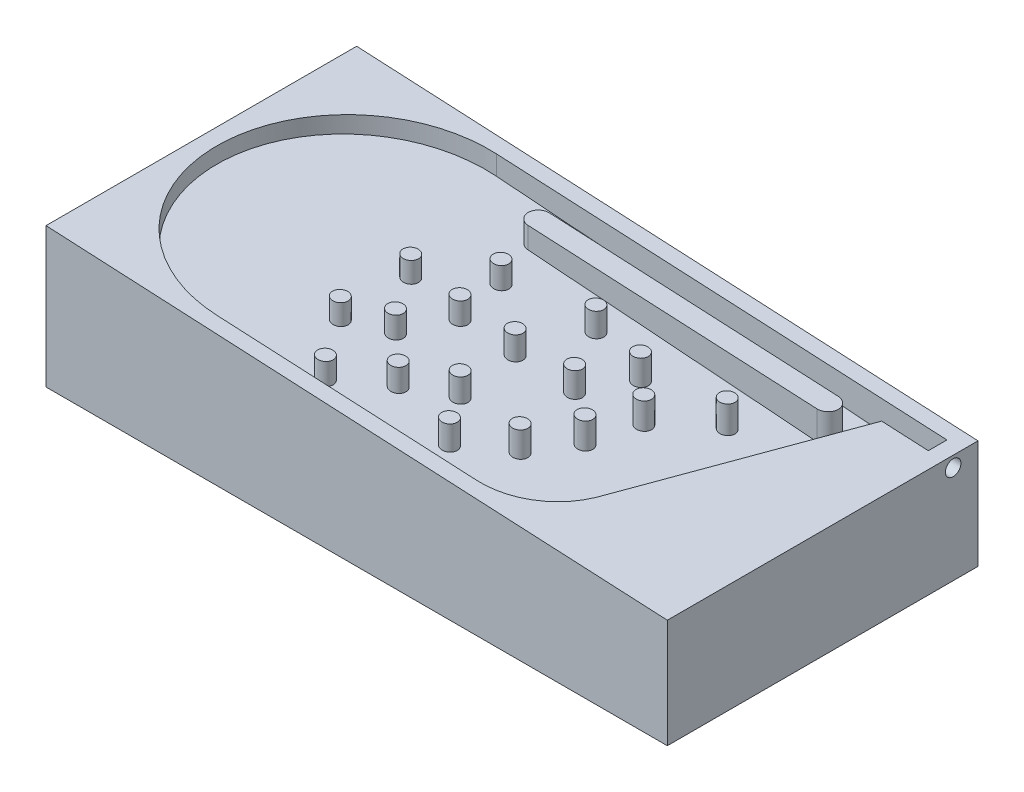
SolidWorks part; units mm, degrees
note: The reader was unsure of these and kept them because the rebuilt part matched: shared geometry of "草圖4<5>".
ref_plane "前基準面" through (0, 0, 0) normal (0, 0, 1) x (1, 0, 0)
ref_plane "上基準面" through (0, 0, 0) normal (0, 1, 0) x (1, 0, 0)
ref_plane "右基準面" through (0, 0, 0) normal (1, 0, 0) x (0, 0, -1)
sketch "草圖2" plane through (0, 0, 0) normal (0, 0, 1) x (1, 0, 0)
  line L0 (0, 0) -> (0, 20)
  line L1 (0, 20) -> (40, 15)
  line L2 (40, 15) -> (40, 0)
  line L3 (40, 0) -> (0, 0)
  dimension "D1" = 20
  dimension "D2" = 15
  dimension "D3" = 40
extrude "填料-伸長1" add sketch "草圖2" along normal blind 20
sketch "草圖4" plane through (1.2355, 0, 0) normal (0, 1, 0) x (1, 0, 0)
  line L0 (8.7645, -1) -> (37.7645, -1)
  line L1 (-1.2355, 0) -> (38.7645, 0)
  line L2 (-1.2355, 0) -> (-1.2355, -20)
  line L3 (-1.2355, -20) -> (38.7645, -20)
  line L4 (38.7645, 0) -> (38.7645, -20)
  line L5 (37.7645, -1) -> (37.7645, -19)
  line L6 (37.7645, -19) -> (8.7645, -19)
  line L7 (30.0533, -15.8981) -> (34.7645, -2.2)
  line L8 (34.7645, -2.2) -> (37.7645, -2.2)
  line L10 (13.5383, -3.0403) -> (32.1165, -3.0403) construction
  line L11 (13.5383, -2.3498) -> (32.1165, -2.3498)
  line L12 (13.5383, -3.7307) -> (32.1165, -3.7307)
  arc A0 (25.5012, -19) -> (30.0533, -15.8981) centre (25.5012, -14.1088) ccw
  arc A1 (8.7645, -1) -> (8.7645, -19) centre (8.7645, -10) ccw
  arc A2 (13.5383, -2.3498) -> (13.5383, -3.7307) centre (13.5383, -3.0403) ccw
  arc A3 (32.1165, -3.7307) -> (32.1165, -2.3498) centre (32.1165, -3.0403) ccw
  circle A4 centre (14.4844, -6.4264) radius 0.5
  circle A5 centre (13.8801, -12.6158) radius 0.5
  circle A6 centre (18.5976, -9.6298) radius 0.5
  circle A7 centre (23.6787, -6.6424) radius 0.5
  circle A8 centre (23.7982, -14.5127) radius 0.5
  circle A9 centre (19.1466, -13.7191) radius 0.5
  circle A10 centre (22.3213, -9.5254) radius 0.5
  circle A11 centre (26.0528, -8.8039) radius 0.5
  circle A12 centre (25.3141, -11.8509) radius 0.5
  circle A13 centre (28.7712, -6.1514) radius 0.5
  circle A14 centre (19.8197, -5.6517) radius 0.5
  circle A15 centre (11.4442, -9.1995) radius 0.5
  circle A16 centre (11.5291, -13.8176) radius 0.5
  circle A17 centre (14.1931, -17.4411) radius 0.5
  circle A18 centre (16.7337, -15.2955) radius 0.5
  circle A19 centre (21.3118, -16.5748) radius 0.5
  circle A20 centre (15.105, -9.6896) radius 0.5
  point P15 (22.8274, -3.0403)
  point P57 (0, 0)
  dimension "D1" = 1
  dimension "D2" = 29
  dimension "D7" = 18
  dimension "D8" = 1
  dimension "D3" = 1
  dimension "D4" = 3
  dimension "D5" = 1.2
  dimension "D6" = 1
sketch "草圖5" plane through (0, 0, 20) normal (0, 0, 1) x (1, 0, 0)
  line L0 (0, 20) -> (40, 15)
  line L1 (40, 15) -> (40, 7)
  line L2 (40, 0) -> (40, 15) construction
  line L3 (0, 20) -> (0, 7)
  line L4 (0, 20) -> (0, 0) construction
  line L5 (0, 7) -> (40, 7)
  point P2 (0, 20)
  point P4 (0, 0)
  point P11 (1.0622, 15)
  dimension "D1" = 8
extrude "除料-伸長6" cut sketch "草圖4" against normal blind 15 from offset 20 contours A1 L6 L5 L0 | A15 | A16 | A17 | A5 | A20 | A4 | A18 | A9 | A19 | A6 | A14 | A10 | A7 | A11 | A12 | A8 | A13 | L12 A3 L11 A2
extrude "填料-伸長2" add sketch "草圖4<5>" along normal blind 10 contours L6 A0 L7 L8 L5
sketch "草圖4<5>" plane through (1.2355, 0, 0) normal (0, 1, 0) x (1, 0, 0) same geometry as "草圖4"
sketch "草圖9" plane through (0, 0, 20) normal (0, 0, 1) x (1, 0, 0)
  line L0 (40, 0) -> (40, 15) construction
  line L1 (0, 0) -> (40, 0)
  line L2 (0, 0) -> (0, 8)
  line L3 (0, 8) -> (40, 5)
  line L4 (40, 0) -> (40, 5)
  dimension "D1" = 8
  dimension "D2" = 5
extrude "填料-伸長3" add sketch "草圖9" against normal blind 20
sketch "草圖11" plane through (0, 0, 20) normal (0, 0, 1) x (1, 0, 0)
  line L0 (0, 10) -> (0, 20)
  line L5 (0, 20) -> (40, 15)
  line L6 (40, 15) -> (40, 10)
  line L7 (40, 10) -> (0, 10)
extrude "除料-伸長7" cut sketch "草圖11" against normal blind 20
sketch "草圖12" plane through (40, 0, 0) normal (1, 0, 0) x (0, 0, -1)
  line L0 (0, 0) -> (0, 10) construction
  line L1 (0, 10) -> (-20, 10) construction
  circle A0 centre (-1.6, 9) radius 0.5
  dimension "D3" = 1
  dimension "D1" = 1.6
  dimension "D2" = 1
extrude "除料-伸長10" cut sketch "草圖12" against normal blind 20
sketch "草圖14" plane through (0, 0, 20) normal (0, 0, 1) x (1, 0, 0)
  line L1 (40, 10) -> (0, 10)
  line L2 (0, 10) -> (0, 9)
  line L3 (0, 9) -> (40, 7)
  line L4 (40, 0) -> (40, 10) construction
  line L8 (40, 10) -> (40, 7)
  point P0 (40, 4.3123)
  dimension "D1" = 3
  dimension "D2" = 1
extrude "除料-伸長15" cut sketch "草圖14" against normal blind 20
sketch "草圖15" plane through (40, 0, 0) normal (1, 0, 0) x (0, 0, -1)
  line L0 (0, 0) -> (0, 7) construction
  line L1 (0, 7) -> (-20, 7) construction
  circle A0 centre (-1.6, 6.3) radius 0.5
  dimension "D1" = 1
  dimension "D2" = 1.6
  dimension "D3" = 0.7
extrude "除料-伸長16" cut sketch "草圖15" against normal blind 1
